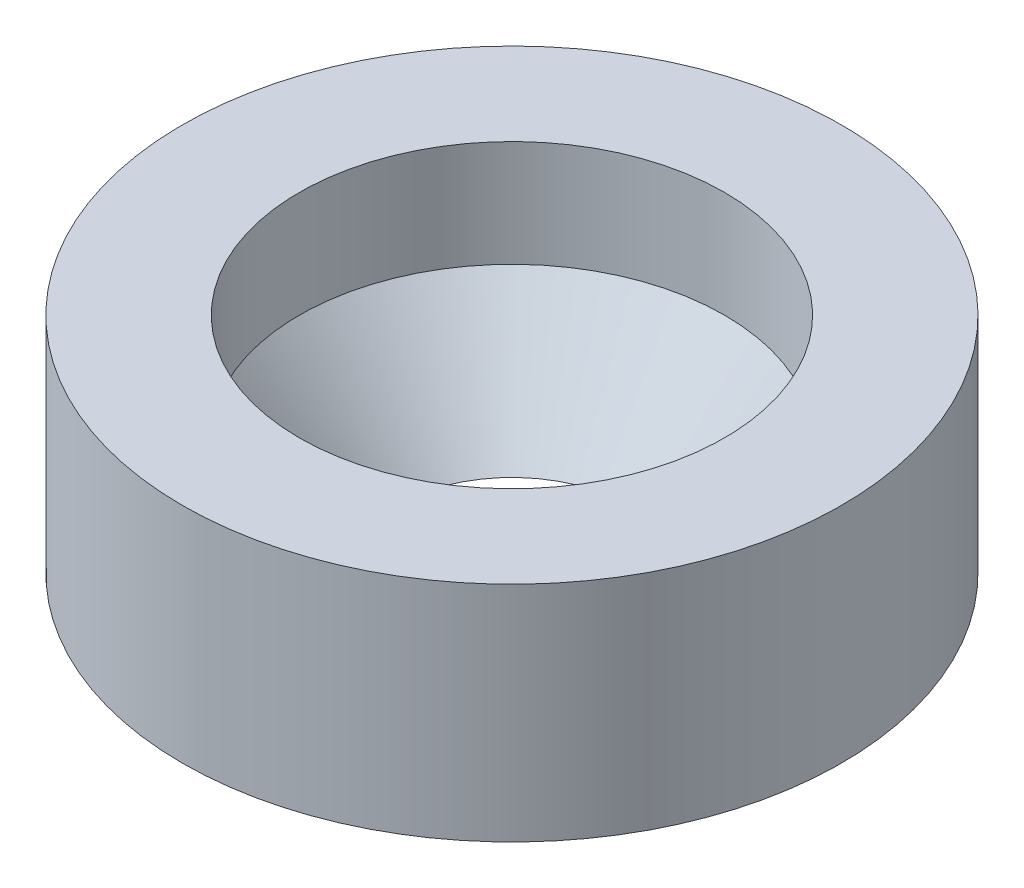
SolidWorks part; units mm, degrees
ref_plane "Front Plane" through (0, 0, 0) normal (0, 0, 1) x (1, 0, 0)
ref_plane "Top Plane" through (0, 0, 0) normal (0, 1, 0) x (1, 0, 0)
ref_plane "Right Plane" through (0, 0, 0) normal (1, 0, 0) x (0, 0, -1)
sketch "Sketch1" plane through (0, 0, 0) normal (1, 0, 0) x (0, 0, -1)
  line L0 (0, 0) -> (2.2, 0) construction
  line L1 (2.2, 0) -> (6.2, 0)
  line L2 (6.2, 0) -> (6.2, 2.2)
  line L3 (6.2, 2.2) -> (4, 2.2)
  line L4 (4, 2.2) -> (2.2, 0)
  line L5 (4, 2.2) -> (0, 2.2) construction
  line L6 (0, 2.2) -> (0, 0) construction
  line L8 (4, 2.2) -> (6.2, 2.2)
  line L9 (4, 2.2) -> (4, 4.2)
  line L10 (4, 4.2) -> (6.2, 4.2)
  line L11 (6.2, 2.2) -> (6.2, 4.2)
  dimension "D1" = 2.2
  dimension "D2" = 4
  dimension "D3" = 4
  dimension "D4" = 2.2
  dimension "D5" = 2
revolve "Revolve1" add sketch "Sketch1" angle 360 about L6 region at (0, 0.9935, -4.6065) region at (0, 3.2, -5.1)
